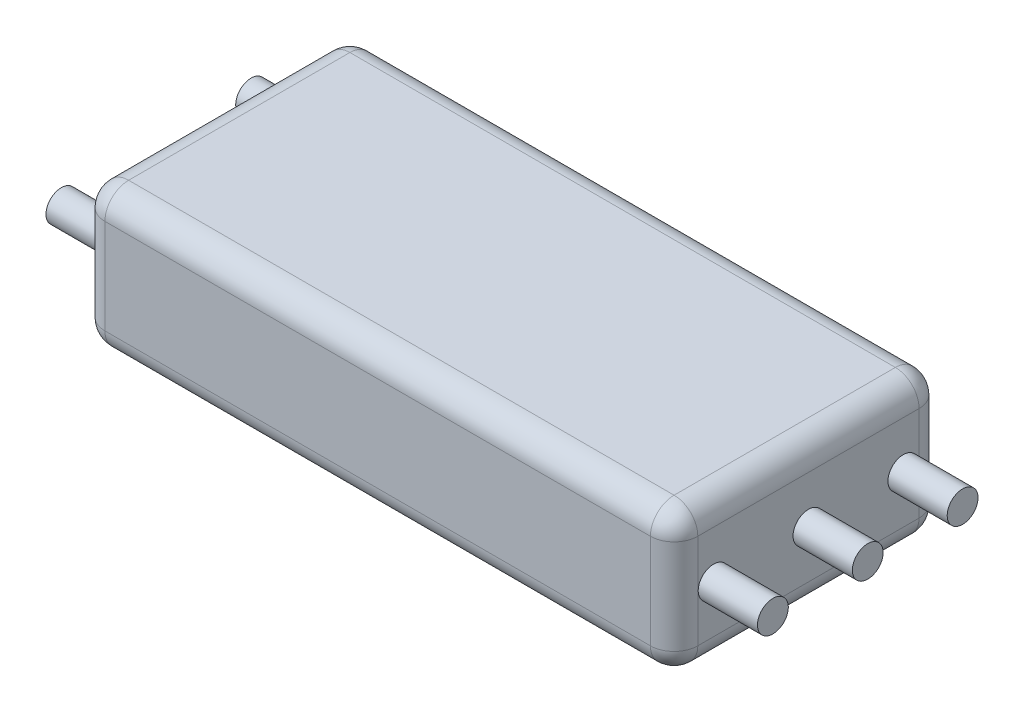
SolidWorks part; units mm, degrees
ref_plane "Front Plane" through (0, 0, 0) normal (0, 0, 1) x (1, 0, 0)
ref_plane "Top Plane" through (0, 0, 0) normal (0, 1, 0) x (1, 0, 0)
ref_plane "Right Plane" through (0, 0, 0) normal (1, 0, 0) x (0, 0, -1)
sketch "Sketch1" plane through (0, 0, 0) normal (0, 1, 0) x (1, 0, 0)
  line L1 (-31.75, -14.3891) -> (31.75, -14.3891)
  line L2 (-31.75, -14.3891) -> (-31.75, 14.3891)
  line L3 (-31.75, 14.3891) -> (31.75, 14.3891)
  line L4 (31.75, -14.3891) -> (31.75, 14.3891)
  line L5 (-31.75, -14.3891) -> (31.75, 14.3891) construction
  line L6 (-31.75, 14.3891) -> (31.75, -14.3891) construction
  point P0 (0, 0)
  dimension "D1" = 63.5
  dimension "D2" = 28.7782
extrude "Boss-Extrude1" add sketch "Sketch1" along normal mid plane 15.24
fillet "Fillet1" radius 2.54 12 edges at (31.75, 0, -14.3891) (-31.75, 0, -14.3891) (-31.75, 0, 14.3891) (31.75, 0, 14.3891) (0, 7.62, 14.3891) (-31.75, 7.62, 0) (0, 7.62, -14.3891) (31.75, 7.62, 0) (0, -7.62, -14.3891) (-31.75, -7.62, 0) (0, -7.62, 14.3891) (31.75, -7.62, 0)
sketch "Sketch2" plane through (0, 0, 0) normal (1, 0, 0) x (0, 0, -1)
  line L0 (0, 8.382) -> (0, -8.382) construction
  circle A0 centre (0, 0) radius 1.651
  circle A1 centre (10.16, 0) radius 1.651
  circle A2 centre (-10.16, 0) radius 1.651
  dimension "D1" = 20.32
  dimension "D2" = 3.302
extrude "Boss-Extrude2" add sketch "Sketch2" along normal blind 6.35 from surface starting at face at (31.75, 0, 0)
extrude "Boss-Extrude3" add sketch "Sketch2<2>" against normal blind 6.35 from surface contours A1 | A2 starting at face at (-31.75, 0, 0)
sketch "Sketch2<2>" plane through (0, 0, 0) normal (1, 0, 0) x (0, 0, -1) same geometry as "Sketch2"
